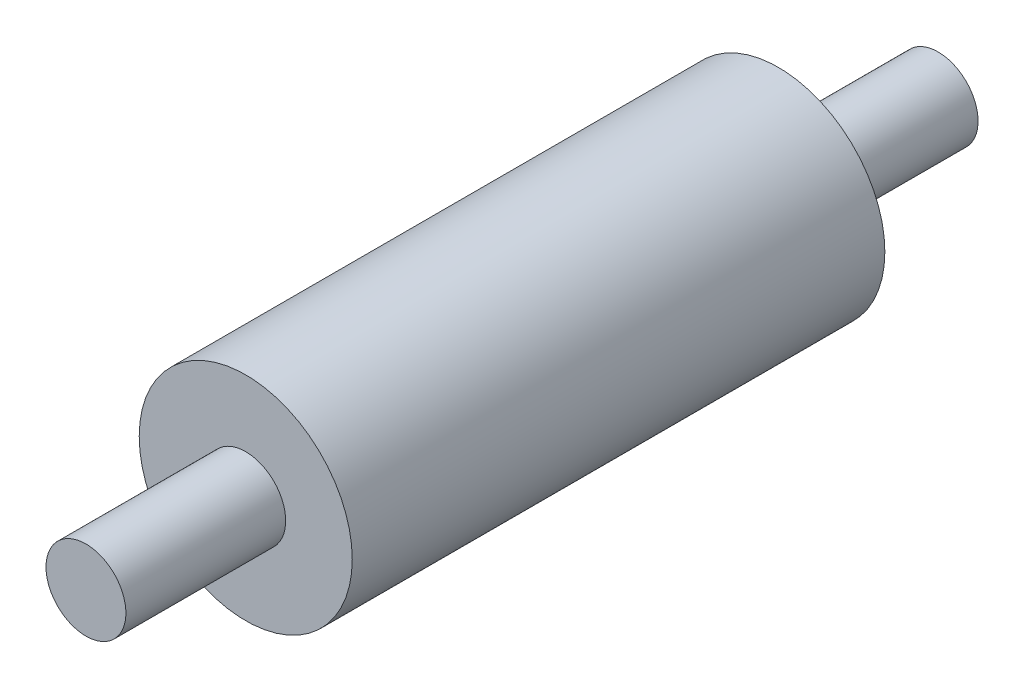
SolidWorks part; units mm, degrees
ref_plane "Front Plane" through (0, 0, 0) normal (0, 0, 1) x (1, 0, 0)
ref_plane "Top Plane" through (0, 0, 0) normal (0, 1, 0) x (1, 0, 0)
ref_plane "Right Plane" through (0, 0, 0) normal (1, 0, 0) x (0, 0, -1)
sketch "Sketch1" plane through (0, 0, 0) normal (0, 0, 1) x (1, 0, 0)
  circle A0 centre (0, 0) radius 20
  dimension "D1" = 40
extrude "Boss-Extrude1" add sketch "Sketch1" along normal blind 100
sketch "Sketch2" plane through (0, 0, 100) normal (0, 0, 1) x (1, 0, 0)
  circle A0 centre (0, 0) radius 7.5
  dimension "D1" = 15
extrude "Boss-Extrude2" add sketch "Sketch2" along normal blind 30
pattern_linear "LPattern1" count 2 spacing 130 along (0, 0, -1) of "Boss-Extrude2"
